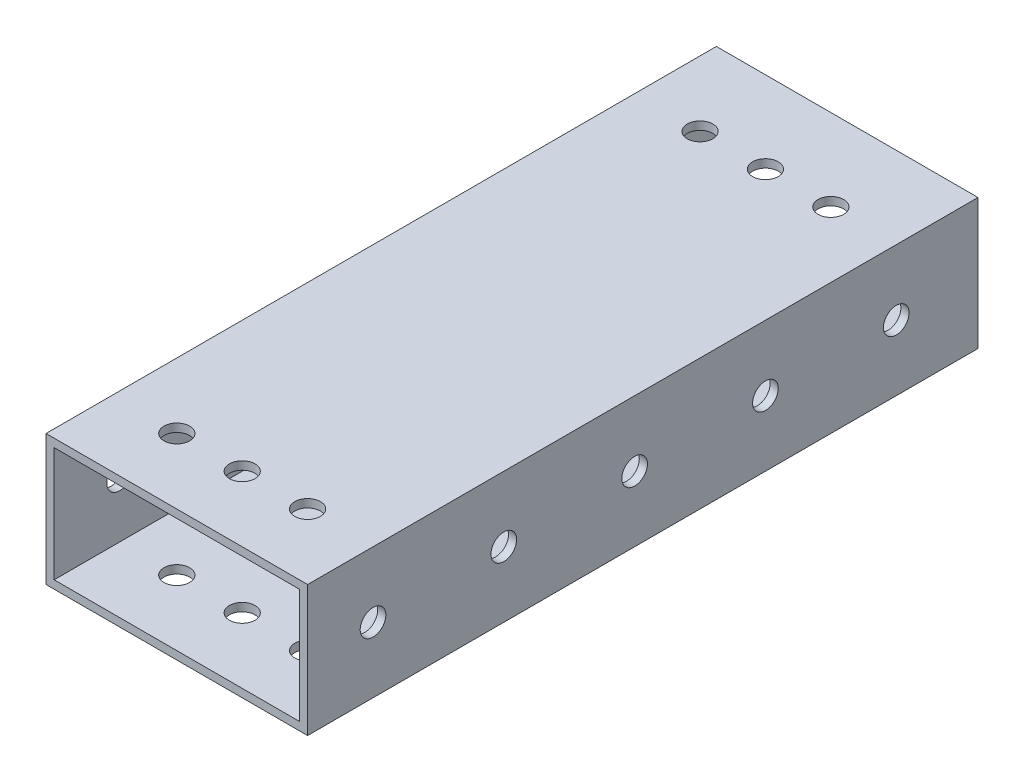
SolidWorks part; units mm, degrees
ref_plane "Front Plane" through (0, 0, 0) normal (0, 0, 1) x (1, 0, 0)
ref_plane "Top Plane" through (0, 0, 0) normal (0, 1, 0) x (1, 0, 0)
ref_plane "Right Plane" through (0, 0, 0) normal (1, 0, 0) x (0, 0, -1)
sketch "Sketch1" plane through (0, 0, 0) normal (0, 0, 1) x (1, 0, 0)
  line L1 (-25.4, -12.7) -> (25.4, -12.7)
  line L2 (-25.4, -12.7) -> (-25.4, 12.7)
  line L3 (-25.4, 12.7) -> (25.4, 12.7)
  line L4 (25.4, -12.7) -> (25.4, 12.7)
  line L5 (-25.4, -12.7) -> (25.4, 12.7) construction
  line L6 (-25.4, 12.7) -> (25.4, -12.7) construction
  line L7 (-23.8125, -11.1125) -> (23.8125, -11.1125)
  line L8 (-23.8125, -11.1125) -> (-23.8125, 11.1125)
  line L9 (-23.8125, 11.1125) -> (23.8125, 11.1125)
  line L10 (23.8125, -11.1125) -> (23.8125, 11.1125)
  line L11 (-23.8125, -11.1125) -> (23.8125, 11.1125) construction
  line L12 (-23.8125, 11.1125) -> (23.8125, -11.1125) construction
  point P0 (0, 0)
  point P6 (0, 0)
  dimension "D1" = 50.8
  dimension "D2" = 25.4
  dimension "D3" = 1.5875
  dimension "D4" = 1.5875
extrude "Boss-Extrude1" add sketch "Sketch1" along normal blind 130.175
sketch "Sketch2" plane through (0, 12.7, 0) normal (0, 1, 0) x (1, 0, 0)
  line L3 (25.4, -130.175) -> (-25.4, -130.175) construction
  circle A0 centre (-12.7, -15.875) radius 2.4892
  circle A1 centre (0, -15.875) radius 2.4892
  circle A2 centre (12.7, -15.875) radius 2.4892
  circle A3 centre (-12.7, -117.475) radius 2.4892
  circle A4 centre (0, -117.475) radius 2.4892
  circle A5 centre (12.7, -117.475) radius 2.4892
  point P12 (0, 0)
  point P13 (0, 0)
  point P14 (0, 0)
  point P15 (0, 0)
  point P16 (0, 0)
  point P17 (0, 0)
  point P19 (17.6635, -10.0853)
  point P20 (0, -5.9292)
  dimension "D1" = 4.9784
  dimension "D2" = 101.6
  dimension "D3" = 12.7
  dimension "D4" = 12.7
  dimension "D5" = 12.7
extrude "Cut-Extrude1" cut sketch "Sketch2" against normal through all
sketch "Sketch3" plane through (25.4, 0, 0) normal (1, 0, 0) x (0, 0, -1)
  line L0 (-130.175, -12.7) -> (-130.175, 12.7) construction
  circle A0 centre (-117.475, 0) radius 2.4892
  circle A1 centre (-92.075, 0) radius 2.4892
  circle A2 centre (-66.675, 0) radius 2.4892
  circle A3 centre (-41.275, 0) radius 2.4892
  circle A4 centre (-15.875, 0) radius 2.4892
  point P5 (-130.175, 0)
  point P7 (-88.9344, 0)
  dimension "D1" = 4.9784
  dimension "D2" = 12.7
  dimension "D4" = 25.4
  dimension "D3" = 5
extrude "Cut-Extrude2" cut sketch "Sketch3" against normal through all
